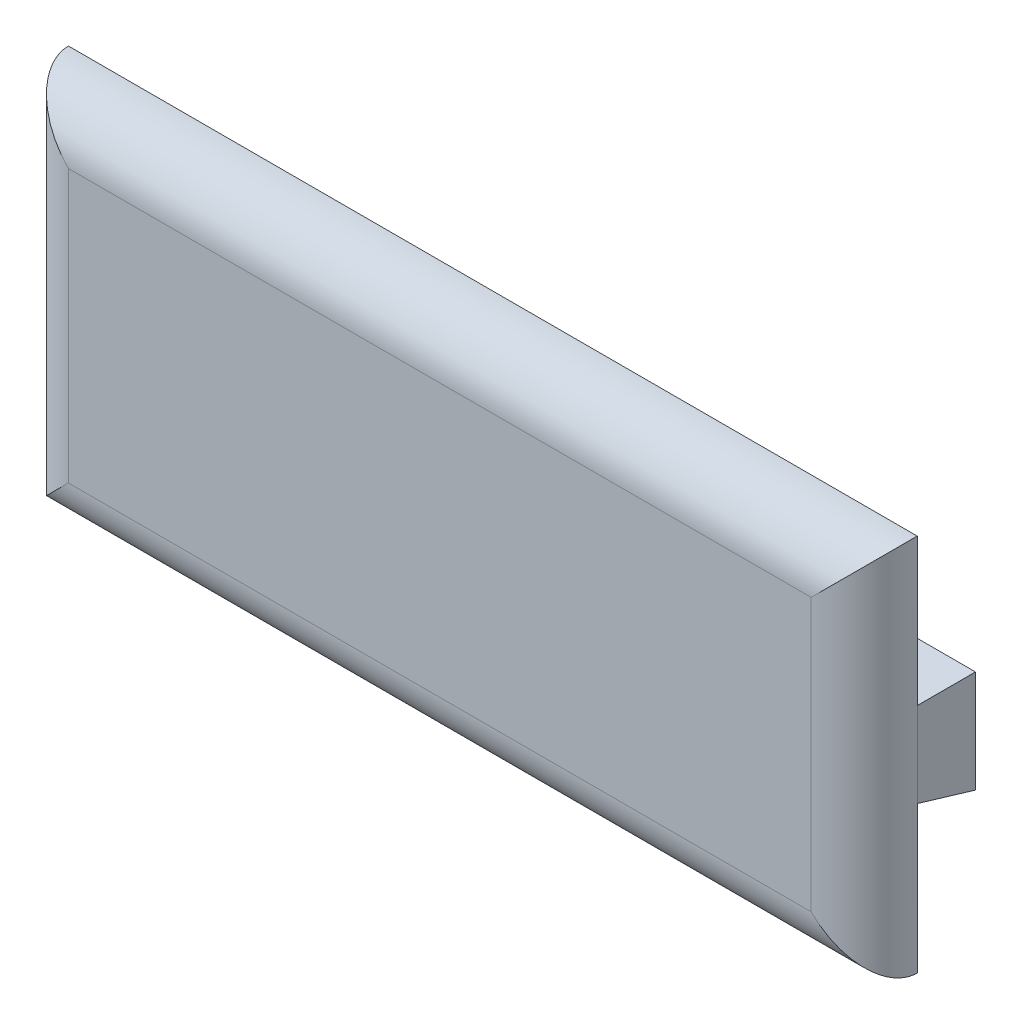
SolidWorks part; units mm, degrees
ref_plane "Front Plane" through (0, 0, 0) normal (0, 0, 1) x (1, 0, 0)
ref_plane "Top Plane" through (0, 0, 0) normal (0, 1, 0) x (1, 0, 0)
ref_plane "Right Plane" through (0, 0, 0) normal (1, 0, 0) x (0, 0, -1)
sketch "Sketch1" plane through (0, 0, 0) normal (0, 0, 1) x (1, 0, 0)
  line L1 (-12, -5.35) -> (12, -5.35)
  line L2 (-12, -5.35) -> (-12, 5.35)
  line L3 (-12, 5.35) -> (12, 5.35)
  line L4 (12, -5.35) -> (12, 5.35)
  line L5 (-12, -5.35) -> (12, 5.35) construction
  line L6 (-12, 5.35) -> (12, -5.35) construction
  point P0 (0, 0)
  dimension "D1" = 24
  dimension "D2" = 10.7
extrude "Boss-Extrude1" add sketch "Sketch1" along normal blind 1.5
sketch "Sketch2" plane through (0, 0, 0) normal (0, 0, -1) x (-1, 0, 0)
  line L0 (-12, -5.35) -> (-12, 5.35) construction
  line L1 (-12, 1.2) -> (12, 1.2)
  line L2 (-12, 1.2) -> (-12, -1.2)
  line L3 (-12, -1.2) -> (12, -1.2)
  line L4 (12, 1.2) -> (12, -1.2)
  line L5 (12, 5.35) -> (12, -5.35) construction
  line L6 (-12, 5.35) -> (0, 1.2) construction
  line L7 (-12, -5.35) -> (0, -1.2) construction
  dimension "D1" = 2.4
extrude "Boss-Extrude2" add sketch "Sketch2" along normal blind 1.4 draft 10 draft outward yes
fillet "Fillet1" radius 1.5 4 edges at (0, -5.35, 1.5) (-12, 0, 1.5) (0, 5.35, 1.5) (12, 0, 1.5)
